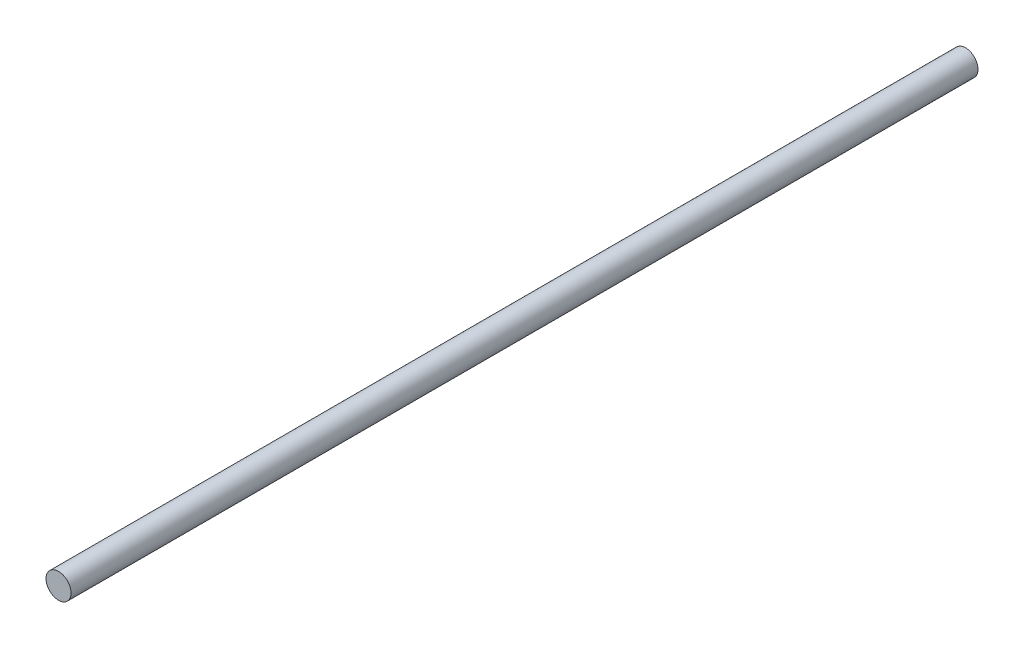
SolidWorks part; units mm, degrees
ref_plane "Front Plane" through (0, 0, 0) normal (0, 0, 1) x (1, 0, 0)
ref_plane "Top Plane" through (0, 0, 0) normal (0, 1, 0) x (1, 0, 0)
ref_plane "Right Plane" through (0, 0, 0) normal (1, 0, 0) x (0, 0, -1)
sketch "Sketch1" plane through (0, 0, 0) normal (0, 0, 1) x (1, 0, 0)
  circle A0 centre (0, 0) radius 1.7526
  dimension "D1" = 3.5052
extrude "Boss-Extrude1" add sketch "Sketch1" along normal blind 127
